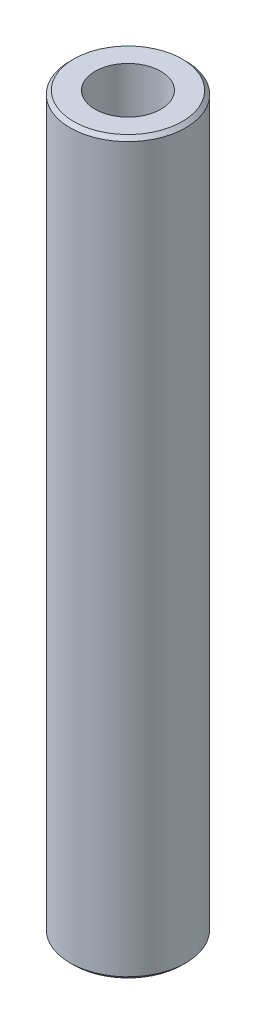
SolidWorks part; units mm, degrees
ref_plane "Front Plane" through (0, 0, 0) normal (0, 0, 1) x (1, 0, 0)
ref_plane "Top Plane" through (0, 0, 0) normal (0, 1, 0) x (1, 0, 0)
ref_plane "Right Plane" through (0, 0, 0) normal (1, 0, 0) x (0, 0, -1)
sketch "Sketch1" plane through (0, 0, 0) normal (0, 1, 0) x (1, 0, 0)
  circle A0 centre (0, 0) radius 47.5
  dimension "SHAFT_OD" = 95
extrude "Boss-Extrude1" add sketch "Sketch1" along normal blind 600
sketch "Sketch2" plane through (0, 0, 0) normal (0, 1, 0) x (1, 0, 0)
  circle A0 centre (0, 0) radius 27.0228
  dimension "BORE_D" = 54.0456
extrude "Cut-Extrude1" cut sketch "Sketch2" along normal through all
chamfer "Chamfer1" distance 2.9544 angle 45 2 edges at (0, 600, 47.5) (0, 0, 47.5)
